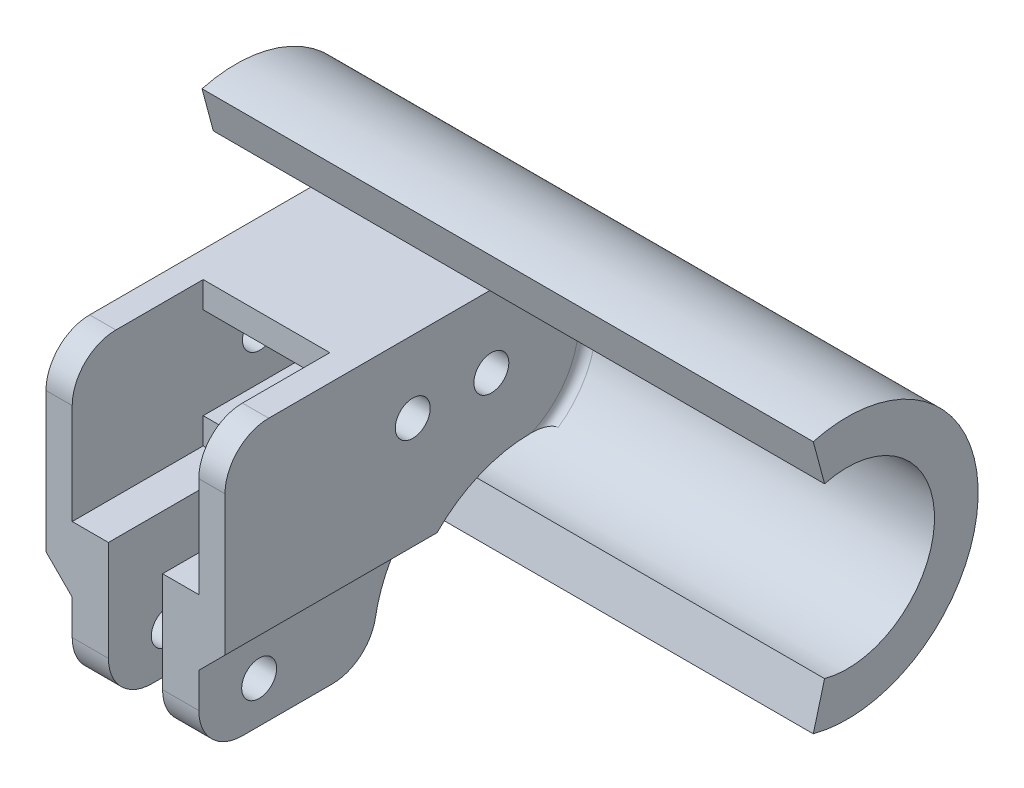
SolidWorks part; units mm, degrees
material "Custom"
ref_plane "Front Plane" through (0, 0, 0) normal (0, 0, 1) x (1, 0, 0)
ref_plane "Top Plane" through (0, 0, 0) normal (0, 1, 0) x (1, 0, 0)
ref_plane "Right Plane" through (0, 0, 0) normal (1, 0, 0) x (0, 0, -1)
sketch "Sketch1" plane through (0, 0, 0) normal (0, 0, 1) x (1, 0, 0)
  line L1 (-7.25, 5.25) -> (7.25, 5.25)
  line L2 (-7.25, 5.25) -> (-7.25, -5.25)
  line L3 (-7.25, -5.25) -> (7.25, -5.25)
  line L4 (7.25, 5.25) -> (7.25, -5.25)
  line L5 (-7.25, 5.25) -> (7.25, -5.25) construction
  line L6 (-7.25, -5.25) -> (7.25, 5.25) construction
  line L7 (-10.25, 8.25) -> (10.25, 8.25)
  line L8 (-10.25, 8.25) -> (-10.25, -8.25)
  line L9 (-10.25, -8.25) -> (10.25, -8.25)
  line L10 (10.25, 8.25) -> (10.25, -8.25)
  line L11 (-10.25, 8.25) -> (10.25, -8.25) construction
  line L12 (-10.25, -8.25) -> (10.25, 8.25) construction
  point P0 (0, 0)
  point P6 (0, 0)
  dimension "D1" = 14.5
  dimension "D2" = 10.5
  dimension "D3" = 20.5
  dimension "D4" = 16.5
extrude "Boss-Extrude1" add sketch "Sketch1" along normal blind 41.5
sketch "Sketch2" plane through (0, 0, 41.5) normal (0, 0, 1) x (1, 0, 0)
  line L0 (10.25, 8.25) -> (-10.25, 8.25) construction
  line L1 (-7.25, 5.25) -> (7.25, 5.25)
  line L2 (-7.25, 5.25) -> (-7.25, 8.25)
  line L3 (-7.25, 8.25) -> (7.25, 8.25)
  line L4 (7.25, 5.25) -> (7.25, 8.25)
  line L5 (-10.25, -8.25) -> (10.25, -8.25) construction
  line L6 (-7.25, -5.25) -> (7.25, -5.25)
  line L7 (-7.25, -5.25) -> (-7.25, -8.25)
  line L8 (-7.25, -8.25) -> (7.25, -8.25)
  line L9 (7.25, -5.25) -> (7.25, -8.25)
  dimension "D1" = 14.5
  dimension "D2" = 14.5
extrude "Cut-Extrude1" cut sketch "Sketch2" against normal blind 15
sketch "Sketch4" plane through (0, 0, 0) normal (1, 0, 0) x (0, 0, -1)
  line L0 (-28.1262, 0) -> (28.1262, 0) construction
  point P4 (0, 0)
ref_plane "Plane1" through (0, 0, 0) normal (-0.6018, -0.7986, 0) x (0, 0, -1)
sketch "Sketch3" plane through (0, 0, 0) normal (1, 0, 0) x (0, 0, -1)
  line L0 (-11.9789, 0) -> (11.9789, 0) construction
  line L1 (-13.8823, -14.4889) -> (-12.5882, -9.6593)
  line L3 (-12.5882, 9.6593) -> (-13.8823, 14.4889)
  line L4 (0, -8.25) -> (0, 8.25) construction
  arc A0 (-12.5882, -9.6593) -> (-12.5882, 9.6593) centre (-10, 0) ccw
  arc A1 (-13.8823, -14.4889) -> (-13.8823, 14.4889) centre (-10, 0) ccw
  point P4 (0, 0)
  dimension "D2" = 10
  dimension "D1" = 150
  dimension "D3" = 5
extrude "Boss-Extrude2" add sketch "Sketch3" along normal blind 50 and the other way blind 20
sketch "Sketch5" plane through (10.25, 0, 0) normal (1, 0, 0) x (0, 0, -1)
  line L0 (-41.5, -8.25) -> (-41.5, 8.25) construction
  circle A0 centre (-20, 0) radius 2
  circle A1 centre (-11, 0) radius 2
  dimension "D1" = 4
  dimension "D2" = 21.5
  dimension "D3" = 9
extrude "Cut-Extrude2" cut sketch "Sketch5" against normal blind 25 contours A0 | A1
sketch "Sketch7" plane through (-10.25, 0, 0) normal (-1, 0, 0) x (0, 0, 1)
  line L0 (41.5, -6) -> (28.5902, -6) construction
  arc A0 (32.2539, -5.5265) -> (34.5902, -6) centre (34.5902, 0) ccw construction
  circle A1 centre (34.5902, -20) radius 2
  dimension "D2" = 4
  dimension "D3" = 12
  dimension "D1" = 20
sketch "Sketch12" plane through (0, -8.25, 0) normal (0, -1, 0) x (1, 0, 0)
  line L1 (-10.25, 41.5) -> (-3.1, 41.5)
  line L2 (-10.25, 41.5) -> (-10.25, 21.5)
  line L3 (-10.25, 21.5) -> (-3.1, 21.5)
  line L4 (-3.1, 41.5) -> (-3.1, 21.5)
  line L5 (10.25, 41.5) -> (3.1, 41.5)
  line L6 (10.25, 41.5) -> (10.25, 21.5)
  line L7 (10.25, 21.5) -> (3.1, 21.5)
  line L8 (3.1, 41.5) -> (3.1, 21.5)
  dimension "D1" = 6.2
  dimension "D2" = 20
extrude "Boss-Extrude16" add sketch "Sketch12" along normal blind 16.5 contours L1 L4 L3 L2 | L5 L8 L7 L6
sketch "Sketch13" plane through (0, -24.75, 0) normal (0, -1, 0) x (1, 0, 0)
  line L0 (-10.25, 41.5) -> (-3.1, 41.5) construction
  line L1 (-10.25, 21.5) -> (-7.25, 21.5)
  line L2 (-10.25, 21.5) -> (-10.25, 41.5)
  line L3 (-10.25, 41.5) -> (-7.25, 41.5)
  line L4 (-7.25, 21.5) -> (-7.25, 41.5)
  line L5 (10.25, 41.5) -> (3.1, 41.5) construction
  line L6 (10.25, 21.5) -> (7.25, 21.5)
  line L7 (10.25, 21.5) -> (10.25, 41.5)
  line L8 (10.25, 41.5) -> (7.25, 41.5)
  line L9 (7.25, 21.5) -> (7.25, 41.5)
  dimension "D1" = 3
extrude "Cut-Extrude5" cut sketch "Sketch13" against normal blind 12
chamfer "Chamfer1" distance 3 angle 45 2 edges at (7.25, -12.75, 31.5) (-7.25, -12.75, 31.5)
fillet "Fillet6" radius 15 2 edges at (6.675, -8.25, 21.5) (-6.675, -8.25, 21.5)
fillet "Fillet7" radius 5 6 edges at (8.75, 8.25, 41.5) (-8.75, 8.25, 41.5) (5.175, -24.75, 21.5) (5.175, -24.75, 41.5) (-5.175, -24.75, 41.5) (-5.175, -24.75, 21.5)
extrude "Cut-Extrude6" cut sketch "Sketch7" against normal through all contours A1
fillet "Fillet14" radius 1 2 edges at (10.25, 0, 0) (-10.25, 0, 0)
